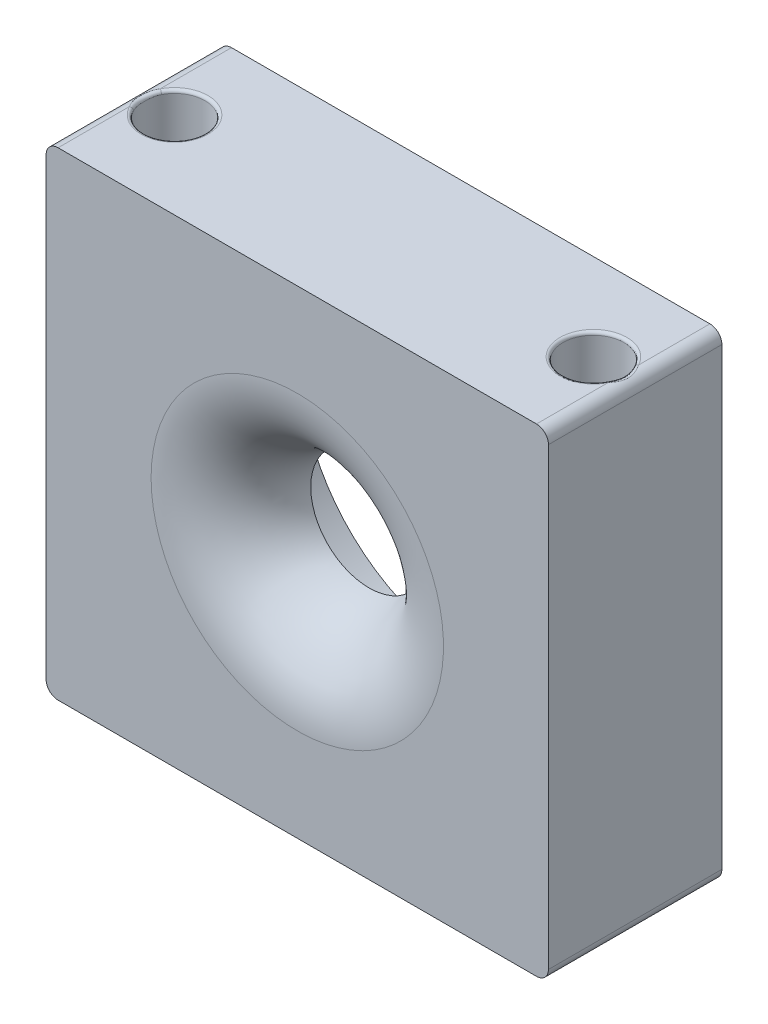
SolidWorks part; units mm, degrees
ref_plane "Front Plane" through (0, 0, 0) normal (1, 0, 0) x (0, 1, 0)
ref_plane "Top Plane" through (0, 0, 0) normal (0, 0, 1) x (0, 1, 0)
ref_plane "Right Plane" through (0, 0, 0) normal (0, 1, 0) x (-1, 0, 0)
sketch "Sketch1" plane through (0, 0, 0) normal (0, 0, 1) x (0, 1, 0)
  line L1 (-40, -42) -> (40, -42)
  line L2 (-40, -42) -> (-40, 42)
  line L3 (-40, 42) -> (40, 42)
  line L4 (40, -42) -> (40, 42)
  line L5 (-40, -42) -> (40, 42) construction
  line L6 (-40, 42) -> (40, -42) construction
  circle A0 centre (0, 0) radius 9.75
  point P0 (0, 0)
  dimension "D3" = 19.5
  dimension "D1" = 84
  dimension "D2" = 80
extrude "Main Boss" add sketch "Sketch1" along normal blind 29
sketch "Sketch2" plane through (0, 0, 0) normal (0, 0, -1) x (1, 0, 0)
  circle A0 centre (0, 0) radius 28.5
  dimension "D1" = 57
extrude "Cut-Extrude1" cut sketch "Sketch2" against normal blind 17
fillet "Fillet1" radius 15 1 edges at (9.75, 0, 29)
sketch "Sketch3" plane through (0, 40, 0) normal (0, 1, 0) x (-1, 0, 0)
  line L0 (-42, 14.5) -> (42, 14.5) construction
  line L1 (-42, 29) -> (-42, 0) construction
  line L2 (42, 29) -> (42, 0) construction
  line L3 (0, 29) -> (0, 0) construction
  line L4 (-42, 29) -> (42, 29) construction
  line L5 (-42, 14.5) -> (-40.125, 14.5)
  circle A0 centre (-35.025, 14.5) radius 5.1
  circle A1 centre (35.025, 14.5) radius 5.1
  dimension "D1" = 10.2
extrude "Screw Head" cut sketch "Sketch3" against normal blind 38 contours A0 | A1 region at (35.025, 40, 14.5) region at (-35.025, 40, 14.5)
sketch "Sketch4" plane through (0, 40, 0) normal (0, 1, 0) x (-1, 0, 0)
  line L1 (-30.3244, 17.8523) -> (-35.5779, 20.247)
  line L2 (-35.5779, 20.247) -> (-40.2785, 16.8947)
  line L3 (-40.2785, 16.8947) -> (-39.7256, 11.1477)
  line L4 (-39.7256, 11.1477) -> (-34.4721, 8.753)
  line L5 (-34.4721, 8.753) -> (-29.7715, 12.1053)
  line L6 (-29.7715, 12.1053) -> (-30.3244, 17.8523)
  circle A0 centre (-35.025, 14.5) radius 5 construction
  circle A1 centre (-35.025, 14.5) radius 5.1 construction
extrude "Nut Slot" cut sketch "Sketch4" against normal blind 4.8 from offset 42 offset against normal yes
sketch "Sketch5" plane through (0, 40, 0) normal (0, 1, 0) x (-1, 0, 0)
  circle A0 centre (-35.025, 14.5) radius 3.2
  circle A1 centre (-35.025, 14.5) radius 5.1 construction
  dimension "D1" = 6.4
extrude "Through Hole" cut sketch "Sketch5" against normal blind 62
mirror "Mirror2" about plane through (0, 0, 0) normal (1, 0, 0) of "Through Hole", "Nut Slot"
fillet "Fillet2" radius 3 1 edges at (-28.5, 0, 17)
fillet "Fillet3" radius 2 4 edges at (-42, 40, 14.5) (-42, -40, 14.5) (42, -40, 14.5) (42, 40, 14.5)
fillet "Fillet4" radius 0.5 4 edges at (-40.0911, 39.9979, 15.0869) (40.0911, 39.9979, 13.9131) (-29.925, 40, 14.5) (29.925, 40, 14.5)
